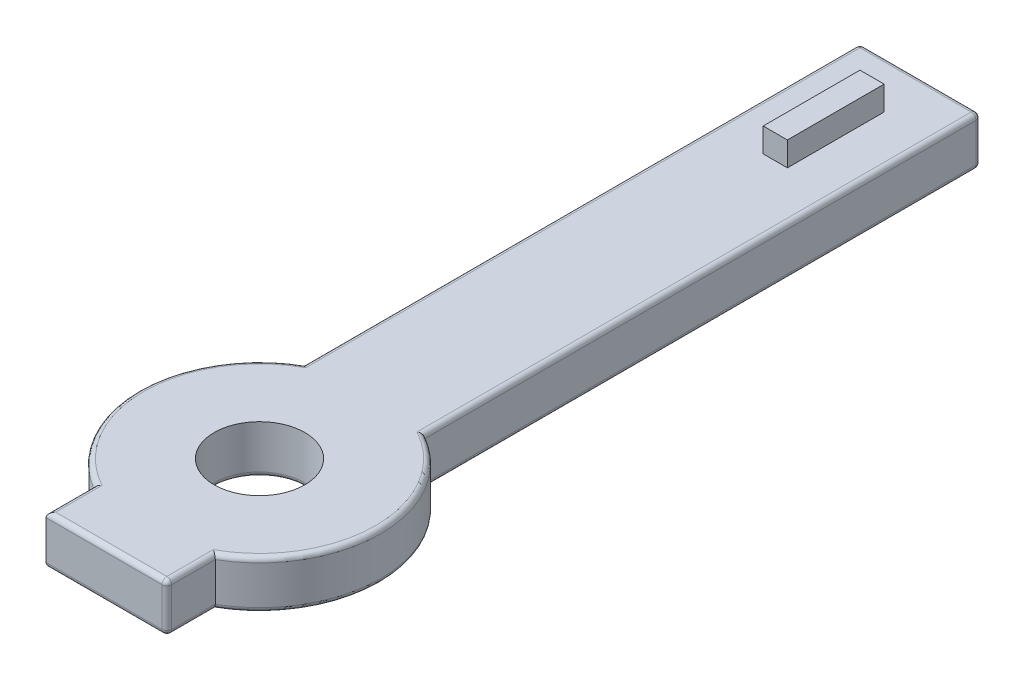
SolidWorks part; units mm, degrees
ref_plane "前视基准面" through (0, 0, 0) normal (0, 0, 1) x (1, 0, 0)
ref_plane "上视基准面" through (0, 0, 0) normal (0, 1, 0) x (1, 0, 0)
ref_plane "右视基准面" through (0, 0, 0) normal (1, 0, 0) x (0, 0, -1)
other "Configuration Table"
sketch "草图1" plane through (0, 0, 0) normal (0, 1, 0) x (1, 0, 0)
  line L0 (-2.5, 27.3301) -> (-2.5, 4.3301)
  line L1 (-2.5, 27.3301) -> (2.5, 27.3301)
  line L2 (2.5, 27.3301) -> (2.5, 4.3301)
  line L3 (0, 0) -> (0, 11.485) construction
  line L4 (-2.5, -4.3301) -> (-2.5, -6.3301)
  line L5 (-2.5, -6.3301) -> (2.5, -6.3301)
  line L6 (2.5, -6.3301) -> (2.5, -4.3301)
  circle A0 centre (0, 0) radius 1.875
  circle A1 centre (0, 0) radius 5
  dimension "D1" = 3.75
  dimension "D2" = 10
  dimension "D3" = 23
  dimension "D4" = 5
  dimension "D5" = 2
extrude "凸台-拉伸1" add sketch "草图1" along normal blind 2 contours A0 A1 | A1 L2 L1 L0 | A1 L4 L5 L6 region at (0, 0, -16.0557) region at (0, 0, -4.8586) region at (0, 0, 5.544)
sketch "草图2" plane through (0, 2, 0) normal (0, 1, 0) x (1, 0, 0)
  line L0 (-2.5, 27.3301) -> (2.5, 27.3301) construction
  line L1 (-0.5, 25.3301) -> (0.5, 25.3301)
  line L2 (-0.5, 25.3301) -> (-0.5, 21.3301)
  line L3 (-0.5, 21.3301) -> (0.5, 21.3301)
  line L4 (0.5, 25.3301) -> (0.5, 21.3301)
  line L5 (2.5, 27.3301) -> (2.5, 4.3301) construction
  line L6 (-2.5, 27.3301) -> (-2.5, 4.3301) construction
  dimension "D1" = 2
  dimension "D2" = 2
  dimension "D3" = 2
  dimension "D4" = 4
extrude "凸台-拉伸2" add sketch "草图2" along normal blind 1
fillet "圆角1" radius 0.2 20 edges at (0, 0, 1.875) (2.5, 0, -15.8301) (0, 0, -27.3301) (-2.5, 0, -15.8301) (-5, 0, 0) (-2.5, 0, 5.3301) (0, 0, 6.3301) (2.5, 0, 5.3301) (5, 0, 0) (2.5, 2, 5.3301) (0, 2, 6.3301) (-2.5, 2, 5.3301) (-5, 2, 0) (-2.5, 2, -15.8301) (0, 2, -27.3301) (2.5, 2, -15.8301) (5, 2, 0) (2.5, 1, 6.3301) (-2.5, 1, -27.3301) (2.5, 1, -27.3301)
